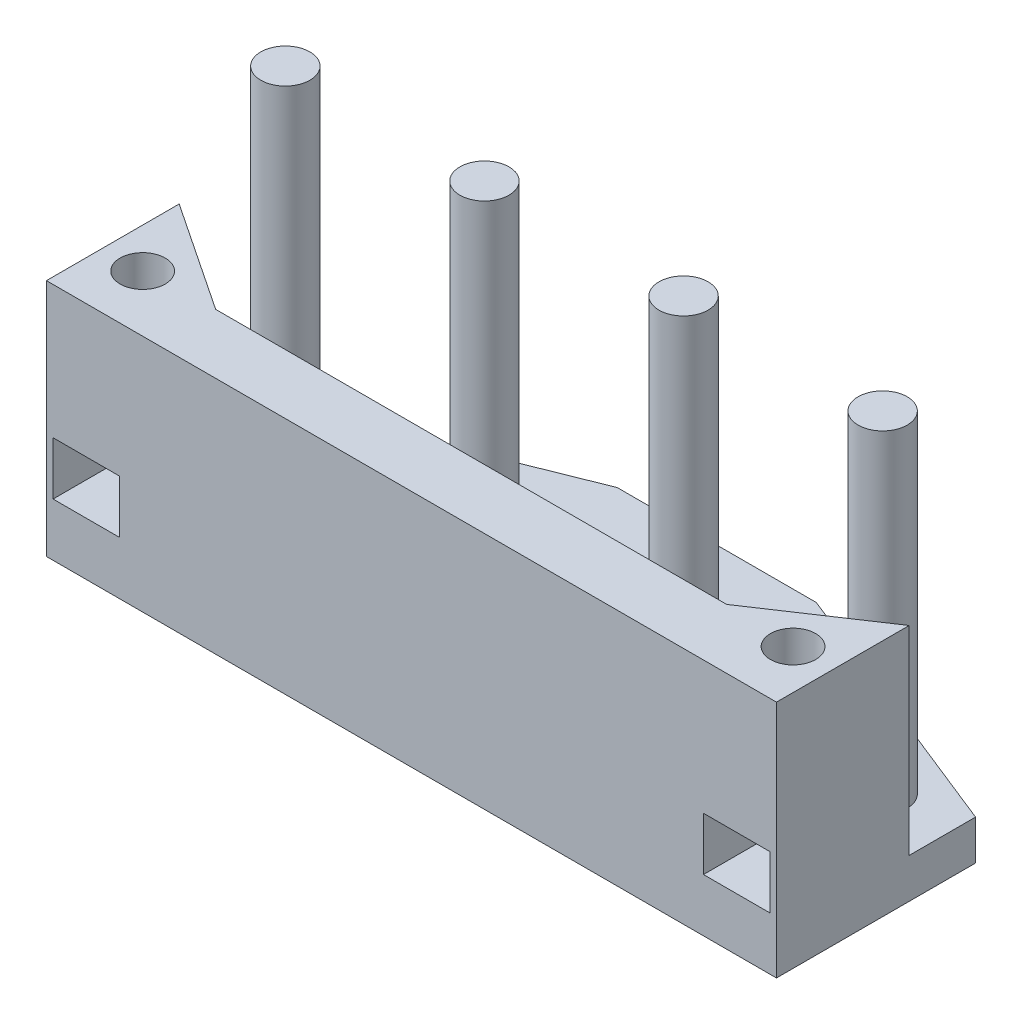
SolidWorks part; units mm, degrees
ref_plane "Front Plane" through (0, 0, 0) normal (0, 0, 1) x (1, 0, 0)
ref_plane "Top Plane" through (0, 0, 0) normal (0, 1, 0) x (1, 0, 0)
ref_plane "Right Plane" through (0, 0, 0) normal (1, 0, 0) x (0, 0, -1)
sketch "Sketch1" plane through (0, 0, 0) normal (0, 1, 0) x (1, 0, 0)
  line L0 (0, 0) -> (55, 0)
  line L1 (55, 0) -> (55, 15)
  line L2 (55, 15) -> (35, 23)
  line L3 (35, 23) -> (20, 23)
  line L4 (20, 23) -> (0, 15)
  line L5 (0, 15) -> (0, 0)
  dimension "D1" = 15
  dimension "D2" = 8
  dimension "D3" = 15
  dimension "D4" = 55
extrude "Boss-Extrude1" add sketch "Sketch1" along normal blind 3
sketch "Sketch2" plane through (0, 3, 0) normal (0, 1, 0) x (1, 0, 0)
  line L0 (6.1696, 13) -> (50006.1696, 13) construction
  line L2 (27.5, 21) -> (27.5, -49979) construction
  line L3 (35, 23) -> (20, 23) construction
  line L4 (20, 13) -> (35, 13)
  line L5 (0, 0) -> (55, 0) construction
  circle A0 centre (5, 13) radius 1.85
  circle A1 centre (20, 13) radius 1.85
  circle A2 centre (35, 13) radius 1.85
  circle A3 centre (50, 13) radius 1.85
  point P11 (27.5, 13)
  point P16 (27.5, 23)
  dimension "D1" = 15
  dimension "D2" = 15
  dimension "D3" = 15
  dimension "D4" = 3.7
  dimension "D5" = 13
extrude "Boss-Extrude2" add sketch "Sketch2" along normal blind 25 contours A0 | A1 | A2 | A3 region at (35, 3, -14.7977) region at (18.2023, 3, -13) region at (5, 3, -13) region at (50, 3, -13)
sketch "Sketch3" plane through (0, 3, 0) normal (0, 1, 0) x (1, 0, 0)
  line L0 (0, 0) -> (15, 0)
  line L1 (0, 0) -> (55, 0) construction
  line L2 (15, 0) -> (0, 10)
  line L3 (0, 15) -> (0, 0) construction
  line L4 (0, 10) -> (0, 0)
  line L5 (55, 0) -> (55, 10)
  line L6 (55, 0) -> (55, 15) construction
  line L7 (55, 10) -> (40, 0)
  line L8 (40, 0) -> (55, 0)
  line L9 (8.25, 4.5) -> (46.75, 4.5)
  line L10 (40, 0) -> (15, 0)
  line M13 (0, 15) -> (0, 0)
  line M14 (0, 0) -> (55, 0)
  line M15 (55, 0) -> (55, 15)
  dimension "D1" = 4.5
  dimension "D2" = 10
  dimension "D3" = 15
extrude "Boss-Extrude3" add sketch "Sketch3" along normal blind 15 contours L2 M14 M13 | L9 L2 L7 M14 | L7 M15 M14 region at (5, 3, -3.3333) region at (27.5, 3, -2.4094) region at (50, 3, -3.3333)
sketch "Sketch4" plane through (0, 18, 0) normal (0, 1, 0) x (1, 0, 0)
  line L0 (55, 0) -> (55, 10) construction
  line L1 (0, 10) -> (0, 0) construction
  line L2 (0, 0) -> (55, 0) construction
  line L3 (20, 2.25) -> (35, 2.25) construction
  line L4 (27.5, 23) -> (27.5, 0) construction
  line L5 (35, 23) -> (20, 23) construction
  circle A0 centre (3, 4.25) radius 1.7
  circle A1 centre (52, 4.25) radius 1.7
  circle A2 centre (20, 2.25) radius 1.7
  circle A3 centre (35, 2.25) radius 1.7
  point P18 (37.2528, 2.25)
  point P19 (27.5, 2.25)
  dimension "D1" = 3.4
  dimension "D2" = 15
  dimension "D3" = 2
  dimension "D4" = 3
  dimension "D5" = 3
  dimension "D6" = 2.25
extrude "Cut-Extrude1" cut sketch "Sketch4" against normal blind 10 contours A0 | A1 region at (3, 18, -4.25) region at (52, 18, -4.25)
sketch "Sketch6" plane through (0, 18, 0) normal (0, 1, 0) x (1, 0, 0)
  line L0 (5.5, 2.8066) -> (5.5, 0)
  line L1 (5.5, 5.6934) -> (3, 7.1368)
  line L2 (3, 7.1368) -> (0.5, 5.6934)
  line L3 (0.5, 5.6934) -> (0.5, 2.8066)
  line L4 (0.5, 2.8066) -> (3, 1.3632)
  line L5 (3, 1.3632) -> (5.5, 2.8066)
  line L6 (5.5, 2.8066) -> (5.5, 5.6934)
  line L7 (52, 7.1368) -> (49.5, 5.6934)
  line L8 (49.5, 5.6934) -> (49.5, 2.8066)
  line L9 (49.5, 2.8066) -> (52, 1.3632)
  line L10 (52, 1.3632) -> (54.5, 2.8066)
  line L11 (54.5, 2.8066) -> (54.5, 5.6934)
  line L12 (54.5, 5.6934) -> (52, 7.1368)
  line L13 (0, 0) -> (55, 0) construction
  line L14 (0.5, 2.8066) -> (0.5, 0)
  line L15 (0.5, 0) -> (5.5, 0)
  line L16 (54.5, 2.8066) -> (54.5, 0)
  line L17 (54.5, 0) -> (49.5, 0)
  line L18 (49.5, 0) -> (49.5, 2.8066)
  circle A0 centre (3, 4.25) radius 2.5 construction
  circle A1 centre (52, 4.25) radius 2.5 construction
  circle M17 centre (52, 4.25) radius 1.7
  line M18 (0, 0) -> (55, 0)
  dimension "D1" = 5
extrude "Cut-Extrude2" cut sketch "Sketch6" against normal blind 4 from offset 10 contours L4 L14 L0 L5 M18 | L18 L16 L10 L9 M18 | L11 L12 L7 L8 L9 L10 M17 | M17 | L1 L2 L3 L4 L5 L6 region at (52, 18, -1.0841) region at (3, 18, -1.0841) region at (49.5764, 18, -4.25) region at (52, 18, -4.25) offset against normal yes
